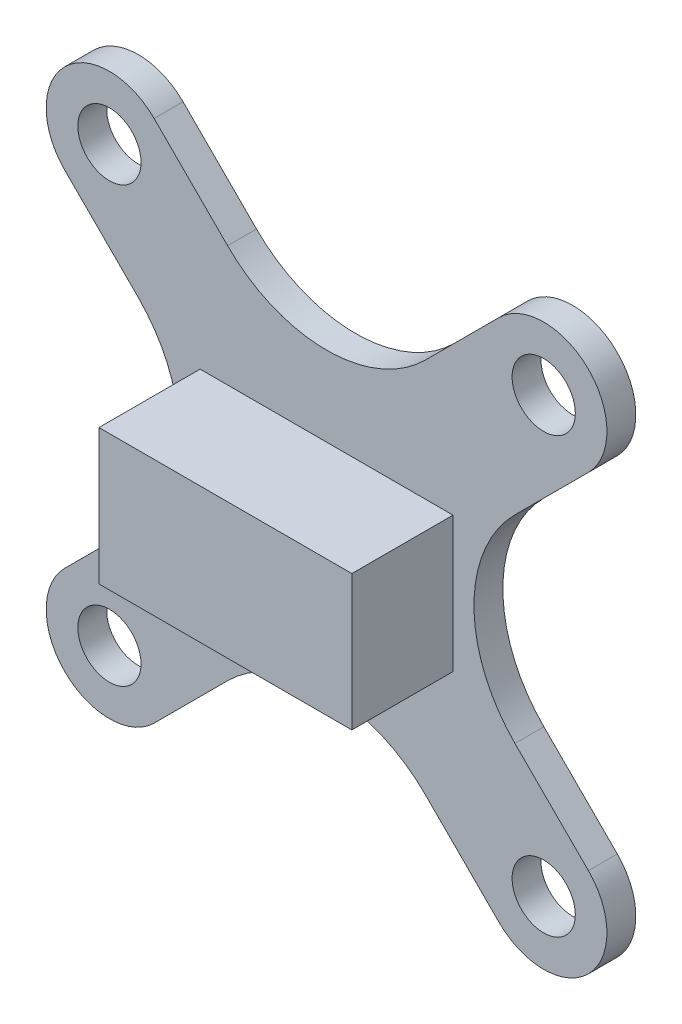
SolidWorks part; units mm, degrees
ref_plane "Front Plane" through (0, 0, 0) normal (0, 0, 1) x (1, 0, 0)
ref_plane "Top Plane" through (0, 0, 0) normal (0, 1, 0) x (1, 0, 0)
ref_plane "Right Plane" through (0, 0, 0) normal (1, 0, 0) x (0, 0, -1)
sketch "Sketch1" plane through (0, 0, 0) normal (0, 0, 1) x (1, 0, 0)
  line L0 (0, 28.0212) -> (0, -27.4834) construction
  line L1 (-27.2065, 0) -> (32.8072, 0) construction
  line L2 (-10.4298, 5.4801) -> (-14.4957, 9.5459)
  line L3 (10.4298, 5.4801) -> (14.4957, 9.5459)
  line L4 (-9.5459, 14.4957) -> (-5.4801, 10.4298)
  line L5 (0, 0) -> (-32.2659, 32.2659) construction
  line L6 (9.5459, 14.4957) -> (5.4801, 10.4298)
  line L7 (-10.4298, -5.4801) -> (-14.4957, -9.5459)
  line L8 (10.4298, -5.4801) -> (14.4957, -9.5459)
  line L9 (9.5459, -14.4957) -> (5.4801, -10.4298)
  line L10 (-9.5459, -14.4957) -> (-5.4801, -10.4298)
  line L12 (-7, 3.75) -> (7, 3.75)
  line L13 (-7, 3.75) -> (-7, -3.75)
  line L14 (-7, -3.75) -> (7, -3.75)
  line L15 (7, 3.75) -> (7, -3.75)
  line L16 (-7, 3.75) -> (7, -3.75) construction
  line L17 (-7, -3.75) -> (7, 3.75) construction
  line L18 (-2.5, 2) -> (2.5, 2)
  line L19 (-2.5, 2) -> (-2.5, -2)
  line L20 (-2.5, -2) -> (2.5, -2)
  line L21 (2.5, 2) -> (2.5, -2)
  line L22 (-2.5, 2) -> (2.5, -2) construction
  line L23 (-2.5, -2) -> (2.5, 2) construction
  circle A0 centre (0, 0) radius 17 construction
  circle A1 centre (-12.0208, 12.0208) radius 1.75
  arc A2 (-14.4957, 9.5459) -> (-9.5459, 14.4957) centre (-12.0208, 12.0208) cw
  circle A3 centre (12.0208, 12.0208) radius 1.75
  arc A4 (14.4957, 9.5459) -> (9.5459, 14.4957) centre (12.0208, 12.0208) ccw
  arc A5 (-14.4957, -9.5459) -> (-9.5459, -14.4957) centre (-12.0208, -12.0208) ccw
  circle A6 centre (-12.0208, -12.0208) radius 1.75
  arc A7 (14.4957, -9.5459) -> (9.5459, -14.4957) centre (12.0208, -12.0208) cw
  circle A8 centre (12.0208, -12.0208) radius 1.75
  arc A9 (-5.4801, 10.4298) -> (5.4801, 10.4298) centre (0, 15.9099) ccw
  arc A11 (-5.4801, -10.4298) -> (5.4801, -10.4298) centre (0, -15.9099) cw
  arc A12 (10.4298, 5.4801) -> (10.4298, -5.4801) centre (15.9099, 0) ccw
  arc A13 (-10.4298, 5.4801) -> (-10.4298, -5.4801) centre (-15.9099, 0) cw
  point P41 (0, 8.1599)
  dimension "D3" = 34
  dimension "D4" = 3.5
  dimension "D5" = 15.5
  dimension "D6" = 16.3198
  dimension "D11" = 41
  dimension "D1" = 7
  dimension "D2" = 45
  dimension "D7" = 14
  dimension "D8" = 7.5
  dimension "D9" = 5
  dimension "D10" = 4
extrude "Boss-Extrude1" add sketch "Sketch1" along normal blind 1.6 contours L2 A13 L7 A5 L10 A11 L9 A7 L8 A12 L3 A4 L6 A9 L4 A2 A6 L12 L15 L14 L13 A1 A3 A8 | L15 L12 L13 L14 region at (-12.1523, 7.8234, 0) region at (0, 3.5912, 0)
extrude "Boss-Extrude2" add sketch "Sketch1<3>" along normal blind 7.2 contours L15 L12 L13 L14 | L19 L20 L21 L18 region at (0, 3.5912, 0)
sketch "Sketch1<3>" plane through (0, 0, 0) normal (0, 0, 1) x (1, 0, 0) same geometry as "Sketch1"
extrude "Boss-Extrude3" add sketch "Sketch1<5>" against normal blind 1.7 contours L21 L18 L19 L20 region at (0, 0, 0)
sketch "Sketch1<5>" plane through (0, 0, 0) normal (0, 0, 1) x (1, 0, 0) same geometry as "Sketch1"
